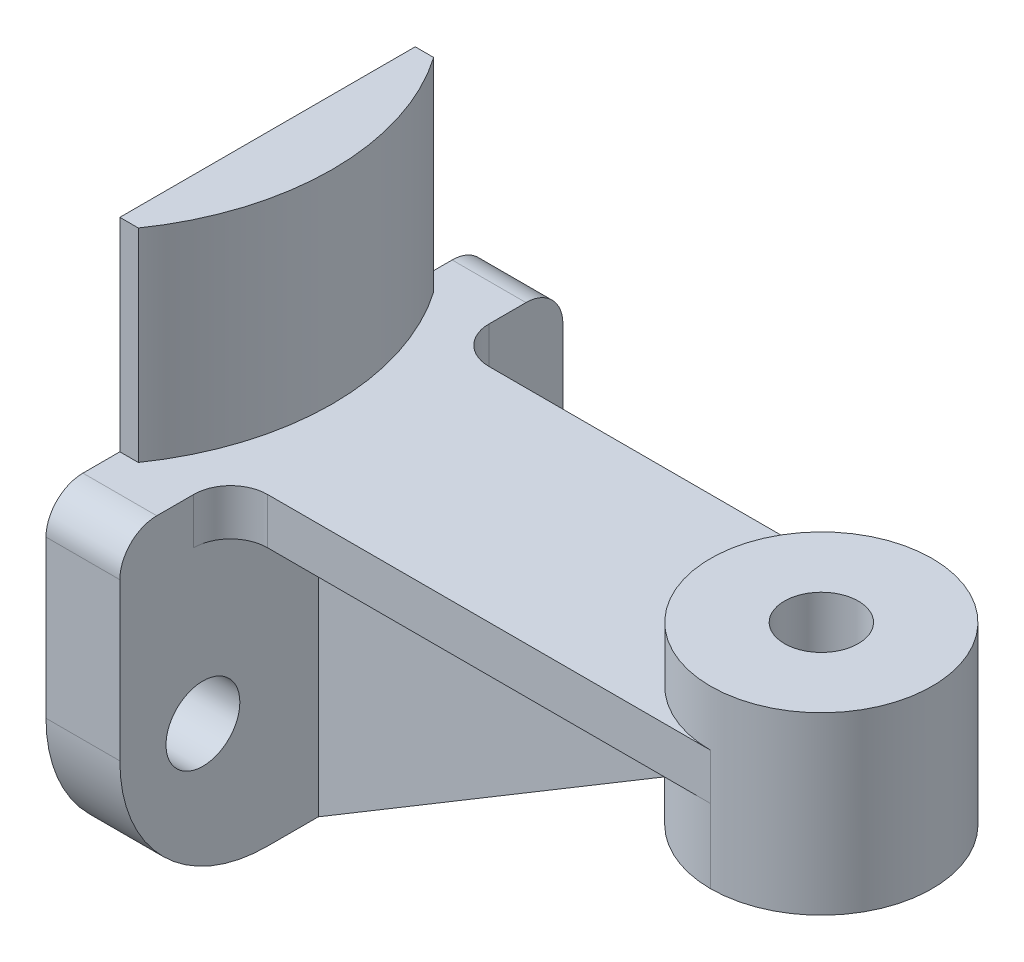
SolidWorks part; units mm, degrees
material "Nylon 6/10"
ref_plane "Front" through (0, 0, 0) normal (0, 0, 1) x (1, 0, 0)
ref_plane "Top" through (0, 0, 0) normal (0, 1, 0) x (1, 0, 0)
ref_plane "Right" through (0, 0, 0) normal (1, 0, 0) x (0, 0, -1)
sketch "Sketch1" plane through (0, 0, 0) normal (1, 0, 0) x (0, 0, -1)
  line L0 (0, 0) -> (76.2, 0)
  line L1 (0, 0) -> (0, 58.7375)
  line L2 (76.2, 58.7375) -> (0, 58.7375)
  line L3 (76.2, 58.7375) -> (76.2, 0)
  dimension "D1" = 76.2
  dimension "D2" = 58.7375
extrude "Base-Extrude" add sketch "Sketch1" along normal blind 12.7
sketch "Sketch2" plane through (12.7, 0, 0) normal (1, 0, 0) x (0, 0, -1)
  line L0 (19.05, 58.7375) -> (57.15, 58.7375)
  line L1 (19.05, 58.7375) -> (19.05, 50.8)
  line L2 (57.15, 50.8) -> (19.05, 50.8)
  line L3 (57.15, 50.8) -> (57.15, 58.7375)
  line L4 (76.2, 58.7375) -> (0, 58.7375) construction
  line L5 (38.1, 58.7375) -> (38.1, 0) construction
  line L6 (0, 0) -> (76.2, 0) construction
  dimension "D1" = 7.9375
  dimension "D2" = 38.1
extrude "Boss-Extrude3" add sketch "Sketch2" along normal offset from surface (82.55 mm away) 95.25 offset beyond the face yes
ref_plane "Plane4" through (0, 68.2625, 0) normal (0, 1, 0) x (-1, 0, 0)
sketch "Sketch4" plane through (0, 68.2625, 0) normal (0, 1, 0) x (-1, 0, 0)
  line L0 (-95.25, -57.15) -> (-95.25, -19.05) construction
  circle A0 centre (-95.25, -38.1) radius 19.05
extrude "Boss-Extrude4" add sketch "Sketch4" against normal blind 30.1625
sketch "Sketch5" plane through (0, 58.7375, 0) normal (0, 1, 0) x (-1, 0, 0)
  line L0 (0, -63.5) -> (-3.175, -63.5)
  line L1 (0, -63.5) -> (0, -12.7)
  line L2 (-3.175, -12.7) -> (0, -12.7)
  line L4 (0, -76.2) -> (0, 0) construction
  arc A0 (-3.175, -12.7) -> (-3.175, -63.5) centre (33.303, -38.1) ccw
  point P6 (0, -38.1)
  dimension "D3" = 44.45
  dimension "D1" = 50.8
  dimension "D2" = 3.175
extrude "Boss-Extrude5" add sketch "Sketch5" along normal blind 34.925
sketch "Sketch6" plane through (0, 0, 0) normal (1, 0, 0) x (0, 0, -1)
  line L0 (63.5, 93.6625) -> (12.7, 93.6625) construction
  line L1 (0, 0) -> (76.2, 0) construction
  point P0 (38.1, 93.6625)
  point P1 (38.1, 0)
sketch "Sketch7" plane through (0, 0, 0) normal (0, 1, 0) x (1, 0, 0)
  line L0 (12.7, 0) -> (12.7, 76.2) construction
  point P0 (12.7, 38.1)
ref_plane "Plane5" through (0, 0, -38.1) normal (0, 0, -1) x (-1, 0, 0)
sketch "Sketch8" plane through (0, 0, -38.1) normal (0, 0, -1) x (-1, 0, 0)
  line L0 (-12.7, 0) -> (-95.25, 49.53)
  line L2 (-12.7, 50.8) -> (-12.7, 0)
  line L3 (-95.25, 50.8) -> (-12.7, 50.8) construction
  line L4 (-95.25, 50.8) -> (-12.7, 50.8)
  line L5 (-95.25, 50.8) -> (-95.25, 49.53)
  line L6 (-95.25, 50.8) -> (-95.25, 58.7375) construction
  point P0 (-76.2, 38.1)
extrude "Boss-Extrude7" add sketch "Sketch8" along normal mid plane 7.9375
sketch "Sketch9" plane through (12.7, 0, 0) normal (1, 0, 0) x (0, 0, -1)
  line L0 (19.05, 58.7375) -> (0, 58.7375) construction
  line L1 (14.2875, 23.8125) -> (61.9125, 23.8125) construction
  line L2 (38.1, 23.8125) -> (38.1, 0) construction
  line L3 (42.0688, 0) -> (34.1313, 0) construction
  circle A0 centre (14.2875, 23.8125) radius 6.35
  circle A1 centre (61.9125, 23.8125) radius 6.35
  dimension "D1" = 12.7
  dimension "D2" = 34.925
  dimension "D3" = 47.625
extrude "Cut-Extrude1" cut sketch "Sketch9" against normal through all
sketch "Sketch10" plane through (0, 68.2625, 0) normal (0, 1, 0) x (-1, 0, 0)
  circle A0 centre (-95.25, -38.1) radius 6.35
  circle A1 centre (-95.25, -38.1) radius 19.05 construction
  dimension "D1" = 12.7
extrude "Cut-Extrude2" cut sketch "Sketch10" against normal through all
sketch "Sketch11" plane through (0, 0, -38.1) normal (0, 0, -1) x (-1, 0, 0)
  line L0 (-101.6, 38.1) -> (-88.9, 38.1) construction
  circle A0 centre (-95.25, 44.45) radius 2.1828
  dimension "D1" = 4.3656
  dimension "D2" = 6.35
extrude "Cut-Extrude3" [suppressed] cut sketch "Sketch11" against normal through all and the other way through all
fillet "Fillet1" radius 6.35 4 edges at (12.7, 54.7687, -57.15) (12.7, 54.7687, -19.05) (6.35, 58.7375, -76.2) (6.35, 58.7375, 0)
fillet "Fillet2" radius 25.4 2 edges at (6.35, 0, -76.2) (6.35, 0, 0)
fillet "Fillet4" [suppressed] radius 1.524
fillet "Fillet5" [suppressed] radius 1.524
fillet "Fillet6" [suppressed] radius 1.524
fillet "Fillet7" [suppressed] radius 1.524
fillet "Fillet10" [suppressed] radius 1.524
fillet "Fillet11" [suppressed] radius 1.524
sketch "Sketch12" [suppressed] plane through (0, 93.6625, 0) normal (0, 1, 0) x (-1, 0, 0)
  line L1 (17.8428, -97.2444) -> (-156.9749, -97.2444)
  line L2 (17.8428, -97.2444) -> (17.8428, 47.2985)
  line L3 (17.8428, 47.2985) -> (-156.9749, 47.2985)
  line L4 (-156.9749, -97.2444) -> (-156.9749, 47.2985)
extrude "Extrude1" [suppressed] add sketch "Sketch12" against normal blind 85.3412 and the other way blind 2.54
